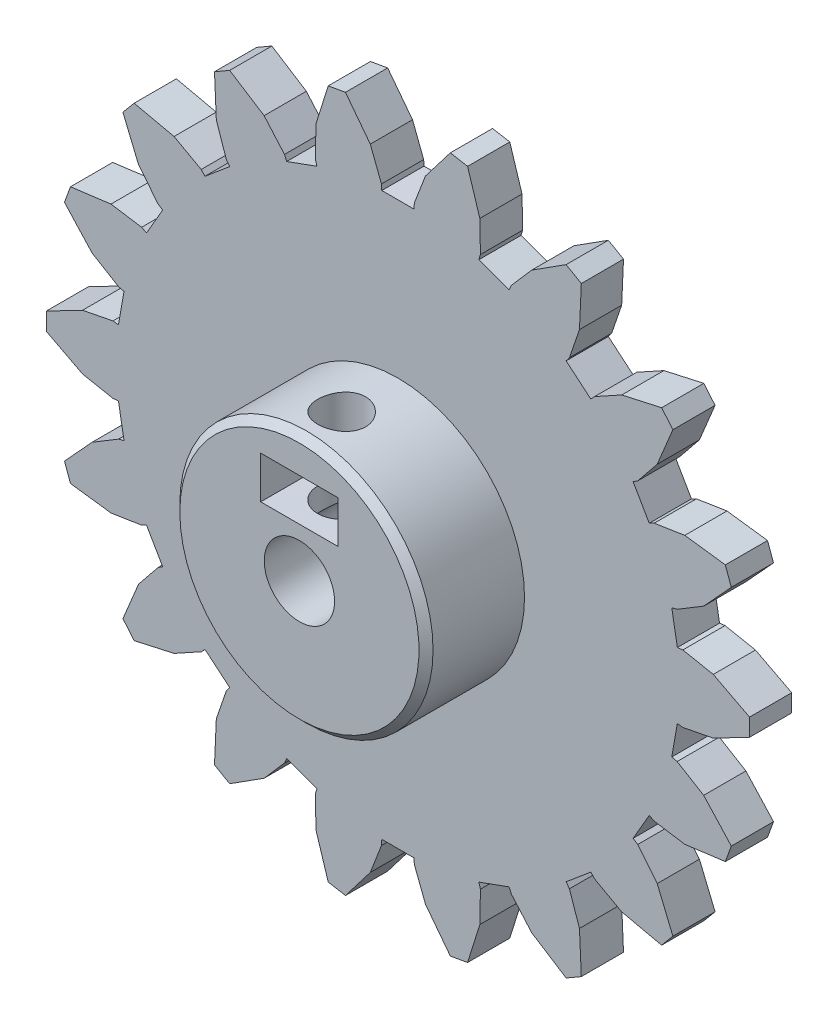
SolidWorks part; units mm, degrees
material "ABS"
ref_plane "Front Plane" through (0, 0, 0) normal (0, 0, 1) x (1, 0, 0)
ref_plane "Top Plane" through (0, 0, 0) normal (0, 1, 0) x (1, 0, 0)
ref_plane "Right Plane" through (0, 0, 0) normal (1, 0, 0) x (0, 0, -1)
sketch "Sketch1" plane through (0, 0, 0) normal (0, 0, 1) x (1, 0, 0)
  line L0 (47.7625, 28.9478) -> (48.1516, 28.9935)
  line L1 (48.1516, 28.9935) -> (50.3142, 28.5692)
  line L2 (50.3142, 28.5692) -> (52.8918, 27.2307)
  line L3 (52.8918, 27.2307) -> (52.8918, 25.9859)
  line L4 (52.8918, 25.9859) -> (50.3142, 24.6474)
  line L5 (50.3142, 24.6474) -> (48.1516, 24.2231)
  line L6 (48.1516, 24.2231) -> (47.7625, 24.2688)
  line L7 (47.7625, 24.2688) -> (47.3647, 22.0134)
  line L8 (47.3647, 22.0134) -> (47.7462, 21.9233)
  line L9 (47.7462, 21.9233) -> (49.6331, 20.785)
  line L10 (49.6331, 20.785) -> (51.5977, 18.6455)
  line L11 (51.5977, 18.6455) -> (51.1718, 17.4756)
  line L12 (51.1718, 17.4756) -> (48.2916, 17.0996)
  line L13 (48.2916, 17.0996) -> (46.1145, 17.4405)
  line L14 (46.1145, 17.4405) -> (45.7645, 17.6166)
  line L15 (45.7645, 17.6166) -> (44.6194, 15.6331)
  line L16 (44.6194, 15.6331) -> (44.9469, 15.4181)
  line L17 (44.9469, 15.4181) -> (46.3307, 13.703)
  line L18 (46.3307, 13.703) -> (47.4452, 11.0207)
  line L19 (47.4452, 11.0207) -> (46.6449, 10.0669)
  line L20 (46.6449, 10.0669) -> (43.8096, 10.6987)
  line L21 (43.8096, 10.6987) -> (41.8805, 11.7635)
  line L22 (41.8805, 11.7635) -> (41.6117, 12.0488)
  line L23 (41.6117, 12.0488) -> (39.8572, 10.5766)
  line L24 (39.8572, 10.5766) -> (40.0916, 10.2624)
  line L25 (40.0916, 10.2624) -> (40.8053, 8.1776)
  line L26 (40.8053, 8.1776) -> (40.9351, 5.276)
  line L27 (40.9351, 5.276) -> (39.857, 4.6534)
  line L28 (39.857, 4.6534) -> (37.4087, 6.2167)
  line L29 (37.4087, 6.2167) -> (35.9601, 7.8772)
  line L30 (35.9601, 7.8772) -> (35.8052, 8.2373)
  line L31 (35.8052, 8.2373) -> (33.653, 7.4539)
  line L32 (33.653, 7.4539) -> (33.7657, 7.0785)
  line L33 (33.7657, 7.0785) -> (33.7233, 4.8753)
  line L34 (33.7233, 4.8753) -> (32.8529, 2.1042)
  line L35 (32.8529, 2.1042) -> (31.6267, 1.8881)
  line L36 (31.6267, 1.8881) -> (29.861, 4.1942)
  line L37 (29.861, 4.1942) -> (29.0677, 6.2501)
  line L38 (29.0677, 6.2501) -> (29.0452, 6.6414)
  line L39 (29.0452, 6.6414) -> (26.755, 6.6414)
  line L40 (26.755, 6.6414) -> (26.7324, 6.2501)
  line L41 (26.7324, 6.2501) -> (25.9392, 4.1942)
  line L42 (25.9392, 4.1942) -> (24.1734, 1.8881)
  line L43 (24.1734, 1.8881) -> (22.9472, 2.1042)
  line L44 (22.9472, 2.1042) -> (22.0768, 4.8753)
  line L45 (22.0768, 4.8753) -> (22.0344, 7.0785)
  line L46 (22.0344, 7.0785) -> (22.1471, 7.4539)
  line L47 (22.1471, 7.4539) -> (19.995, 8.2373)
  line L48 (19.995, 8.2373) -> (19.84, 7.8772)
  line L49 (19.84, 7.8772) -> (18.3914, 6.2167)
  line L50 (18.3914, 6.2167) -> (15.9432, 4.6534)
  line L51 (15.9432, 4.6534) -> (14.865, 5.276)
  line L52 (14.865, 5.276) -> (14.9948, 8.1776)
  line L53 (14.9948, 8.1776) -> (15.7085, 10.2624)
  line L54 (15.7085, 10.2624) -> (15.943, 10.5766)
  line L55 (15.943, 10.5766) -> (14.1884, 12.0488)
  line L56 (14.1884, 12.0488) -> (13.9196, 11.7635)
  line L57 (13.9196, 11.7635) -> (11.9905, 10.6987)
  line L58 (11.9905, 10.6987) -> (9.1553, 10.0669)
  line L59 (9.1553, 10.0669) -> (8.355, 11.0207)
  line L60 (8.355, 11.0207) -> (9.4694, 13.703)
  line L61 (9.4694, 13.703) -> (10.8533, 15.4181)
  line L62 (10.8533, 15.4181) -> (11.1808, 15.6331)
  line L63 (11.1808, 15.6331) -> (10.0357, 17.6166)
  line L64 (10.0357, 17.6166) -> (9.6856, 17.4405)
  line L65 (9.6856, 17.4405) -> (7.5085, 17.0996)
  line L66 (7.5085, 17.0996) -> (4.6283, 17.4756)
  line L67 (4.6283, 17.4756) -> (4.2024, 18.6455)
  line L68 (4.2024, 18.6455) -> (6.1671, 20.785)
  line L69 (6.1671, 20.785) -> (8.054, 21.9233)
  line L70 (8.054, 21.9233) -> (8.4355, 22.0134)
  line L71 (8.4355, 22.0134) -> (8.0377, 24.2688)
  line L72 (8.0377, 24.2688) -> (7.6485, 24.2231)
  line L73 (7.6485, 24.2231) -> (5.4859, 24.6474)
  line L74 (5.4859, 24.6474) -> (2.9083, 25.9859)
  line L75 (2.9083, 25.9859) -> (2.9083, 27.2307)
  line L76 (2.9083, 27.2307) -> (5.4859, 28.5692)
  line L77 (5.4859, 28.5692) -> (7.6485, 28.9935)
  line L78 (7.6485, 28.9935) -> (8.0377, 28.9478)
  line L79 (8.0377, 28.9478) -> (8.4355, 31.2032)
  line L80 (8.4355, 31.2032) -> (8.054, 31.2933)
  line L81 (8.054, 31.2933) -> (6.1671, 32.4315)
  line L82 (6.1671, 32.4315) -> (4.2024, 34.5711)
  line L83 (4.2024, 34.5711) -> (4.6283, 35.741)
  line L84 (4.6283, 35.741) -> (7.5085, 36.117)
  line L85 (7.5085, 36.117) -> (9.6856, 35.7761)
  line L86 (9.6856, 35.7761) -> (10.0357, 35.6)
  line L87 (10.0357, 35.6) -> (11.1808, 37.5835)
  line L88 (11.1808, 37.5835) -> (10.8533, 37.7985)
  line L89 (10.8533, 37.7985) -> (9.4694, 39.5136)
  line L90 (9.4694, 39.5136) -> (8.355, 42.1959)
  line L91 (8.355, 42.1959) -> (9.1553, 43.1497)
  line L92 (9.1553, 43.1497) -> (11.9905, 42.5179)
  line L93 (11.9905, 42.5179) -> (13.9196, 41.4531)
  line L94 (13.9196, 41.4531) -> (14.1884, 41.1678)
  line L95 (14.1884, 41.1678) -> (15.943, 42.64)
  line L96 (15.943, 42.64) -> (15.7085, 42.9541)
  line L97 (15.7085, 42.9541) -> (14.9948, 45.0389)
  line L98 (14.9948, 45.0389) -> (14.865, 47.9406)
  line L99 (14.865, 47.9406) -> (15.9432, 48.5632)
  line L100 (15.9432, 48.5632) -> (18.3914, 46.9999)
  line L101 (18.3914, 46.9999) -> (19.84, 45.3394)
  line L102 (19.84, 45.3394) -> (19.995, 44.9793)
  line L103 (19.995, 44.9793) -> (22.1471, 45.7627)
  line L104 (22.1471, 45.7627) -> (22.0344, 46.1381)
  line L105 (22.0344, 46.1381) -> (22.0768, 48.3413)
  line L106 (22.0768, 48.3413) -> (22.9472, 51.1123)
  line L107 (22.9472, 51.1123) -> (24.1734, 51.3285)
  line L108 (24.1734, 51.3285) -> (25.9392, 49.0224)
  line L109 (25.9392, 49.0224) -> (26.7324, 46.9665)
  line L110 (26.7324, 46.9665) -> (26.755, 46.5752)
  line L111 (26.755, 46.5752) -> (29.0452, 46.5752)
  line L112 (29.0452, 46.5752) -> (29.0677, 46.9665)
  line L113 (29.0677, 46.9665) -> (29.861, 49.0224)
  line L114 (29.861, 49.0224) -> (31.6267, 51.3285)
  line L115 (31.6267, 51.3285) -> (32.8529, 51.1123)
  line L116 (32.8529, 51.1123) -> (33.7233, 48.3413)
  line L117 (33.7233, 48.3413) -> (33.7657, 46.1381)
  line L118 (33.7657, 46.1381) -> (33.653, 45.7627)
  line L119 (33.653, 45.7627) -> (35.8052, 44.9793)
  line L120 (35.8052, 44.9793) -> (35.9601, 45.3394)
  line L121 (35.9601, 45.3394) -> (37.4087, 46.9999)
  line L122 (37.4087, 46.9999) -> (39.857, 48.5632)
  line L123 (39.857, 48.5632) -> (40.9351, 47.9406)
  line L124 (40.9351, 47.9406) -> (40.8053, 45.0389)
  line L125 (40.8053, 45.0389) -> (40.0916, 42.9541)
  line L126 (40.0916, 42.9541) -> (39.8572, 42.64)
  line L127 (39.8572, 42.64) -> (41.6117, 41.1678)
  line L128 (41.6117, 41.1678) -> (41.8805, 41.4531)
  line L129 (41.8805, 41.4531) -> (43.8096, 42.5179)
  line L130 (43.8096, 42.5179) -> (46.6449, 43.1497)
  line L131 (46.6449, 43.1497) -> (47.4452, 42.1959)
  line L132 (47.4452, 42.1959) -> (46.3307, 39.5136)
  line L133 (46.3307, 39.5136) -> (44.9469, 37.7985)
  line L134 (44.9469, 37.7985) -> (44.6194, 37.5835)
  line L135 (44.6194, 37.5835) -> (45.7645, 35.6)
  line L136 (45.7645, 35.6) -> (46.1145, 35.7761)
  line L137 (46.1145, 35.7761) -> (48.2916, 36.117)
  line L138 (48.2916, 36.117) -> (51.1718, 35.741)
  line L139 (51.1718, 35.741) -> (51.5977, 34.5711)
  line L140 (51.5977, 34.5711) -> (49.6331, 32.4315)
  line L141 (49.6331, 32.4315) -> (47.7462, 31.2933)
  line L142 (47.7462, 31.2933) -> (47.3647, 31.2032)
  line L143 (47.3647, 31.2032) -> (47.7625, 28.9478)
  line L144 (27.9001, 46.5752) -> (27.9001, 6.6414) construction
  line L145 (52.8918, 26.6083) -> (2.9083, 26.6083) construction
sketch "Sketch2" plane through (0, 0, 0) normal (0, 0, 1) x (1, 0, 0)
  line L0 (27.9001, 46.5752) -> (27.9001, 6.6414) construction
  line L1 (52.8918, 26.6083) -> (2.9083, 26.6083) construction
  circle A0 centre (27.9001, 26.6083) radius 9
  point P0 (27.9001, 26.6083)
  dimension "D1" = 18
sketch "Sketch3" plane through (0, 0, 0) normal (0, 0, 1) x (1, 0, 0)
  circle A0 centre (27.9001, 26.6083) radius 2.5
  dimension "D1" = 5
extrude "Boss-Extrude1" add sketch "Sketch1" along normal blind 3
extrude "Boss-Extrude2" add sketch "Sketch2" along normal offset from surface (10 mm away) 7 up to face at (27.9001, 26.6083, 3) offset beyond the face yes
extrude "Cut-Extrude1" cut sketch "Sketch3" along normal through all
ref_axis "Axis1" through (27.9001, 26.6083, 10) along (0, 0, -1)
ref_plane "Plane1" through (0, 26.6083, 0) normal (0, 1, 0) x (1, 0, 0)
sketch "Sketch4" plane through (0, 26.6083, 0) normal (0, 1, 0) x (1, 0, 0)
  line L0 (27.9001, -10) -> (27.9001, 0) construction
  line L1 (18.9001, -10) -> (36.9001, -10) construction
  circle A0 centre (27.9001, -7) radius 1.7
  dimension "D1" = 3.4
  dimension "D2" = 3
extrude "Cut-Extrude2" cut sketch "Sketch4" along normal through all
sketch "Sketch6" plane through (0, 0, 10) normal (0, 0, 1) x (1, 0, 0)
  line L0 (27.9001, 35.6083) -> (27.9001, 17.6083) construction
  line L2 (25.1501, 33.1083) -> (30.6501, 33.1083)
  line L3 (25.1501, 33.1083) -> (25.1501, 30.1083)
  line L4 (25.1501, 30.1083) -> (30.6501, 30.1083)
  line L5 (30.6501, 33.1083) -> (30.6501, 30.1083)
  line L6 (25.1501, 33.1083) -> (30.6501, 30.1083) construction
  line L7 (25.1501, 30.1083) -> (30.6501, 33.1083) construction
  circle A0 centre (27.9001, 26.6083) radius 9 construction
  circle A1 centre (27.9001, 26.6083) radius 9 construction
  point P7 (27.9001, 31.6083)
  point P12 (27.9001, 26.6083)
  dimension "D1" = 5.5
  dimension "D2" = 3
  dimension "D3" = 5
extrude "Cut-Extrude3" cut sketch "Sketch6" against normal blind 6
chamfer "Chamfer1" distance 0.5 angle 45 1 edges at (18.9001, 26.6083, 10)
ref_axis "Axis2" through (27.9001, 26.6083, 10) along (0, 0, -1)
